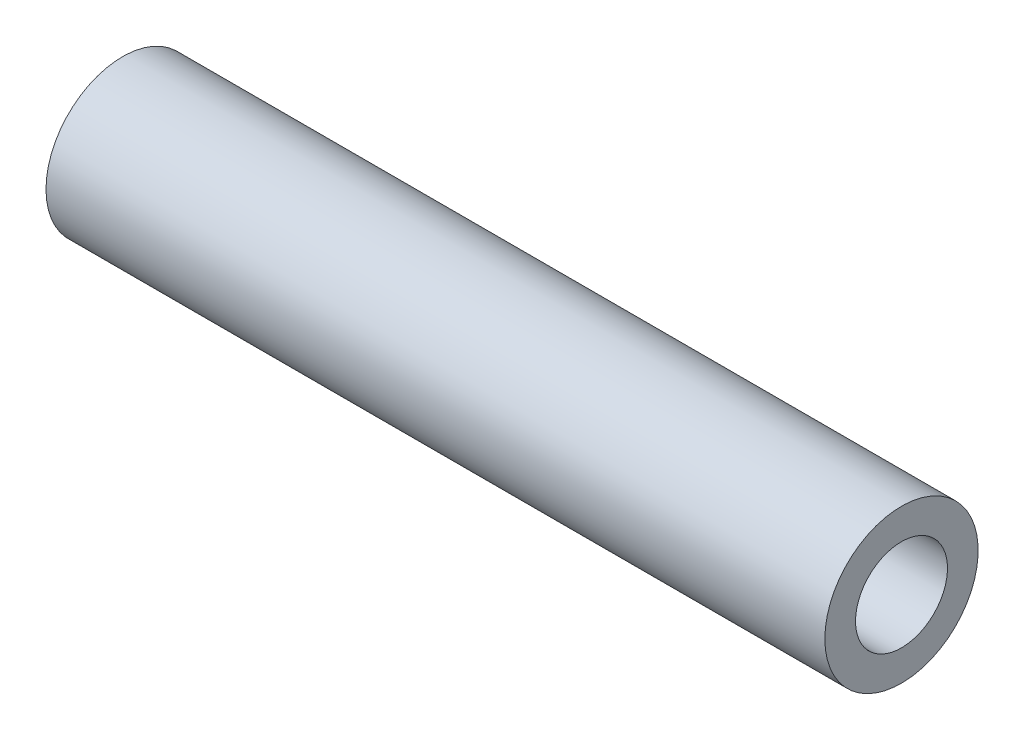
SolidWorks part; units mm, degrees
material "Alloy Steel"
ref_plane "Front Plane" through (0, 0, 0) normal (0, 0, 1) x (1, 0, 0)
ref_plane "Top Plane" through (0, 0, 0) normal (0, 1, 0) x (1, 0, 0)
ref_plane "Right Plane" through (0, 0, 0) normal (1, 0, 0) x (0, 0, -1)
sketch "Sketch2" plane through (0, 0, 0) normal (0, 1, 0) x (1, 0, 0)
  line L0 (0, 5) -> (40.8, 5)
  line L1 (40.8, 5) -> (40.8, 6)
  line L2 (40.8, 6) -> (50.8, 6)
  line L3 (50.8, 6) -> (50.8, 10)
  line L4 (50.8, 10) -> (0, 10)
  line L5 (0, 10) -> (0, 5)
  line L6 (0, 0) -> (64.4269, 0) construction
  line L7 (0, 0) -> (0, 5) construction
  point P9 (45.8367, 7.3256)
  dimension "D1" = 20
  dimension "D2" = 101.6
  dimension "D3" = 10
  dimension "D4" = 12
  dimension "D5" = 10
revolve "Revolve1" add sketch "Sketch2" angle 360 about L6
mirror "Mirror1" about plane through (0, 0, -10) normal (1, 0, 0) of "Revolve1"
equation "\"D1@Sketch2\"=20mm"
equation "\"D2@Sketch2\"=4in"
equation "\"D3@Sketch2\"=10mm"
